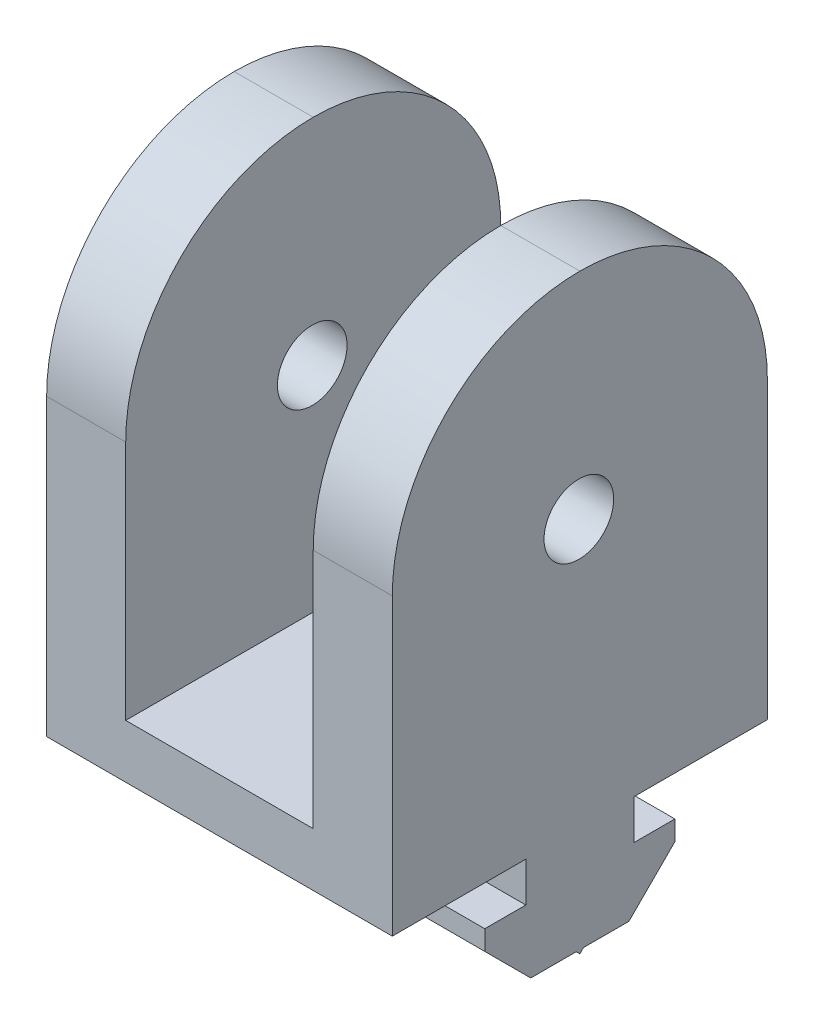
SolidWorks part; units mm, degrees
material "Beech"
ref_plane "Front Plane" through (0, 0, 0) normal (0, 0, 1) x (1, 0, 0)
ref_plane "Top Plane" through (0, 0, 0) normal (0, 1, 0) x (1, 0, 0)
ref_plane "Right Plane" through (0, 0, 0) normal (1, 0, 0) x (0, 0, -1)
sketch "Sketch1" plane through (0, 0, 0) normal (0, 1, 0) x (1, 0, 0)
  line L1 (-60.7745, 29.9716) -> (89.2255, 29.9716)
  line L2 (-60.7745, 29.9716) -> (-60.7745, -40.0284)
  line L3 (-60.7745, -40.0284) -> (89.2255, -40.0284)
  line L4 (89.2255, 29.9716) -> (89.2255, -40.0284)
  dimension "D1" = 150
  dimension "D2" = 70
extrude "Boss-Extrude1" add sketch "Sketch1" along normal blind 10
sketch "Sketch2" plane through (0, 10, 0) normal (0, 1, 0) x (1, 0, 0)
  line L0 (89.2255, 29.9716) -> (-60.7745, 29.9716) construction
  line L1 (-40.7745, 29.9716) -> (-22.7745, 29.9716)
  line L2 (-40.7745, 29.9716) -> (-40.7745, -40.0284)
  line L3 (-40.7745, -40.0284) -> (-22.7745, -40.0284)
  line L4 (-22.7745, 29.9716) -> (-22.7745, -40.0284)
  line L5 (-60.7745, -40.0284) -> (89.2255, -40.0284) construction
  line L6 (-60.7745, 29.9716) -> (-60.7745, -40.0284) construction
  line L7 (12.2255, 29.9716) -> (30.2255, 29.9716)
  line L8 (12.2255, 29.9716) -> (12.2255, -40.0284)
  line L9 (12.2255, -40.0284) -> (30.2255, -40.0284)
  line L10 (30.2255, 29.9716) -> (30.2255, -40.0284)
  dimension "D1" = 18
  dimension "D2" = 35
  dimension "D3" = 18
  dimension "D4" = 20
extrude "Boss-Extrude2" add sketch "Sketch2" along normal blind 80
fillet "Fillet1" radius 35 4 edges at (21.2255, 90, 40.0284) (21.2255, 90, -29.9716) (-31.7745, 90, -29.9716) (-31.7745, 90, 40.0284)
sketch "Sketch3" plane through (-40.7745, 0, 0) normal (-1, 0, 0) x (0, 0, 1)
  line L0 (-29.9716, 10) -> (40.0284, 10) construction
  circle A0 centre (5.212, 50) radius 6.5
  dimension "D1" = 13
  dimension "D2" = 40
extrude "Cut-Extrude1" cut sketch "Sketch3" against normal through all
sketch "Sketch5" plane through (0, 0, 0) normal (0, 0, 1) x (1, 0, 0)
  line L0 (30.2255, 40.3886) -> (74.056, 10)
  line L1 (30.2255, 55) -> (30.2255, 10) construction
  line L2 (30.2255, 10) -> (89.2255, 10) construction
rib "Rib1" sketch "Sketch5" sketch "Sketch5" thickness 40 extrusion direction parallel to sketch draft on no parameters "D1"=40
sketch "Sketch7" plane through (0, 10, 0) normal (0, 1, 0) x (1, 0, 0)
  line L0 (30.2255, -5.0284) -> (30.2255, 9.9716)
  line L1 (30.2255, -5.0284) -> (30.2255, 29.9716) construction
  line L2 (30.2255, 20) -> (30.2255, 29.9716) construction
  line L3 (30.2255, 20) -> (74.056, 20)
  line L4 (30.2255, 20) -> (30.2255, 9.9716)
  line L5 (30.2255, 9.9716) -> (74.056, 9.9716)
  line L6 (74.056, 20) -> (74.056, 9.9716)
  line L7 (74.056, -20) -> (74.056, 20) construction
  line M8 (30.2255, 20) -> (74.056, 20)
  line M9 (74.056, 20) -> (74.056, -20)
  dimension "D1" = 15
extrude "Cut-Extrude2" cut sketch "Sketch7" along normal blind 80 contours L4 L5 M9 M8 region at (52.1407, 10, -14.9858)
scale "Scale1" scale about origin uniform scaling yes scale factor 0.31
sketch "Sketch11" plane through (0, 0, -9.2912) normal (0, 0, -1) x (-1, 0, 0)
  line L0 (1.6351, 3.1) -> (1.6351, 27.8689) construction
  line L1 (-3.7899, 3.1) -> (7.0601, 3.1) construction
  line L2 (-8.3649, 3.1) -> (-8.3649, 27.9)
  line L3 (-9.3699, 3.1) -> (12.6401, 3.1)
  line L4 (-9.3699, 3.1) -> (-9.3699, 27.9)
  line L5 (-9.3699, 27.9) -> (12.6401, 27.9)
  line L6 (12.6401, 3.1) -> (12.6401, 27.9)
  line L7 (11.6351, 3.1) -> (11.6351, 27.9)
  line L8 (-8.3649, 3.1) -> (-8.3649, 0)
  line L9 (-27.6599, 0) -> (18.8401, 0) construction
  line L10 (11.6351, 3.1) -> (11.6351, 0)
  line L11 (-27.6599, 0) -> (18.8401, 0) construction
  line L15 (-22.9574, 3.1) -> (-9.3699, 3.1)
  line L16 (-9.3699, 3.1) -> (-9.3699, 12.5205)
  line L17 (-9.3699, 12.5205) -> (-22.9574, 3.1)
  line L18 (-22.9574, 3.1) -> (-9.3699, 3.1)
  line L19 (-9.3699, 3.1) -> (-9.3699, 12.5205)
  line L20 (-9.3699, 12.5205) -> (-22.9574, 3.1)
  line M4 (-3.7899, 17.05) -> (-9.3699, 17.05)
  line M5 (-9.3699, 17.05) -> (-9.3699, 3.1)
  line M6 (-9.3699, 3.1) -> (-27.6599, 3.1)
  line M7 (-27.6599, 3.1) -> (-27.6599, 0)
  line M8 (-27.6599, 0) -> (18.8401, 0)
  line M21 (-27.6599, 0) -> (18.8401, 0)
  line M22 (18.8401, 0) -> (18.8401, 3.1)
  line M23 (18.8401, 3.1) -> (12.6401, 3.1)
  line M24 (12.6401, 3.1) -> (12.6401, 17.05)
  line M25 (12.6401, 17.05) -> (7.0601, 17.05)
  dimension "D1" = 10
  dimension "D2" = 0
extrude "Cut-Extrude5" cut sketch "Sketch11" against normal up to surface (21.7 mm away) contours L4 L3 L2 M5 M4 | L5 L4 L2 M4 | L4 L20 M6 | L8 L3 M6 M7 M8 | L7 L3 M24 M25 | L7 L6 L5 M25 | L3 L10 M21 M22 M23 region at (8.8674, 10.075, -9.2912) region at (18.0124, 1.55, -9.2912) region at (8.8674, 22.475, -9.2912) region at (13.899, 6.2402, -9.2912) region at (-12.1376, 10.075, -9.2912) region at (-15.2376, 1.55, -9.2912) region at (-12.1376, 22.475, -9.2912)
sketch "Sketch13" plane through (8.3649, 0, 0) normal (1, 0, 0) x (0, 0, -1)
  line L0 (-1.5588, 0) -> (-1.5588, 27.9) construction
  line L1 (-12.4088, 0) -> (9.2912, 0) construction
  line L2 (1.5662, 0) -> (1.5662, -2.3)
  line L7 (-4.6838, 0) -> (-7.0588, 0)
  line L8 (-4.6838, 0) -> (-4.6838, -2.3)
  line L9 (-4.6838, -2.3) -> (-7.0588, -2.3)
  line L10 (-7.0588, 0) -> (-7.0588, -2.3)
  line L11 (1.5662, -2.3) -> (3.9412, -2.3)
  line B0 (-1.5588, -10) -> (-1.5588, 0) construction
  line B1 (-1.5588, -6.31) -> (-1.7688, -6.1)
  line B2 (-1.7688, -6.1) -> (-4.3981, -6.1)
  line B3 (-4.3981, -6.1) -> (-7.0588, -3.4393)
  line B4 (-7.0588, -3.4393) -> (-7.0588, -1.8)
  line B5 (-7.0588, -1.8) -> (-4.6838, -1.8)
  line B6 (-4.6838, -1.8) -> (-4.6838, -1.455)
  line B7 (-4.6838, -1.455) -> (-6.1388, 0)
  line B8 (-6.1388, 0) -> (3.0212, 0)
  line B9 (-1.5588, -10) -> (-7.472, -4.0868) construction
  line B10 (1.5662, -1.455) -> (3.0212, 0)
  line B11 (1.5662, -1.8) -> (1.5662, -1.455)
  line B12 (3.9412, -1.8) -> (1.5662, -1.8)
  line B13 (3.9412, -3.4393) -> (3.9412, -1.8)
  line B14 (1.2805, -6.1) -> (3.9412, -3.4393)
  line B15 (-1.3488, -6.1) -> (1.2805, -6.1)
  line B16 (-1.5588, -6.31) -> (-1.3488, -6.1)
  line M12 (-12.4088, 0) -> (9.2912, 0)
  dimension "D1" = 0.5
sketch_block_instance "V Slot 1-4"
sketch_block "V Slot 1" parameters "D1"=10, "D2"=11, "D3"=4.3, "D4"=1.8, "D5"=0.21, "D6"=45, "D7"=9.16, "D8"=1.5, "D9"=6.25
extrude "Boss-Extrude3" add sketch "Sketch13" against normal blind 20 contours B1 B16 B15 B14 B13 L11 L2 B8 L8 L9 B4 B3 B2 M12 region at (8.3649, -3.1636, 1.5588)
